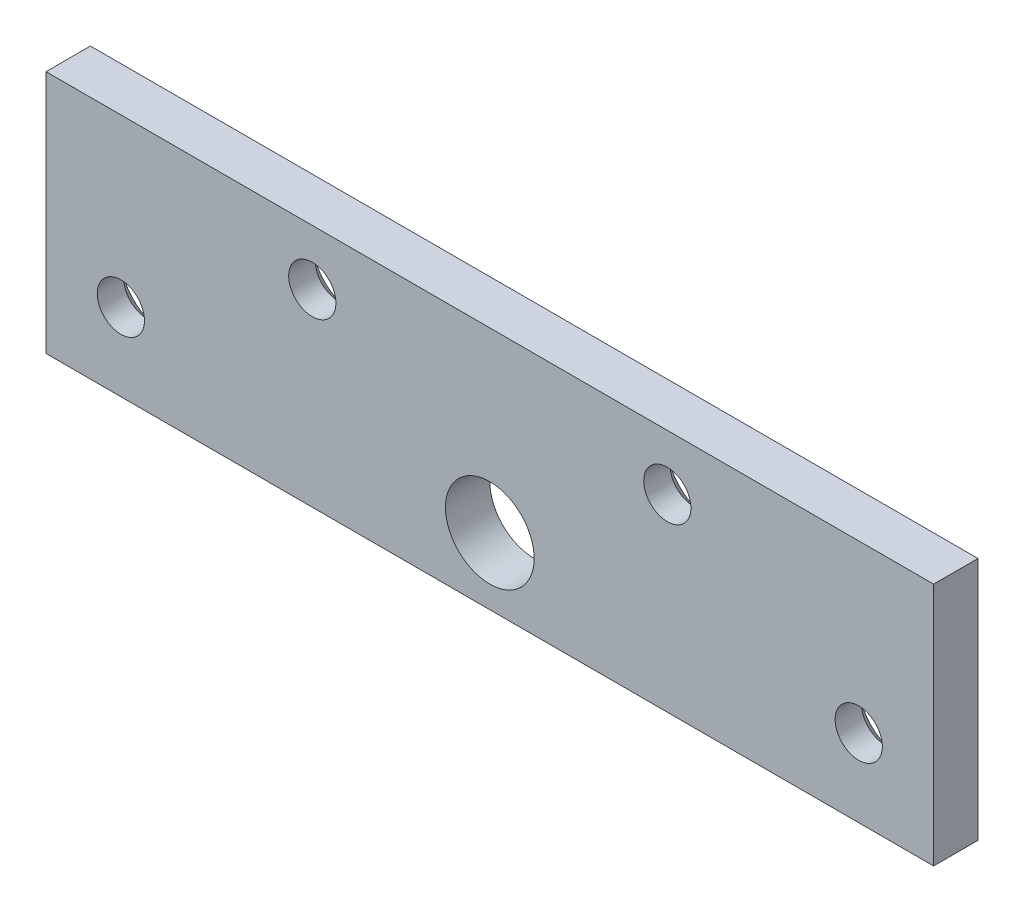
SolidWorks part; units mm, degrees
material "6061-T6 (SS)"
ref_plane "Front Plane" through (0, 0, 0) normal (0, 0, 1) x (1, 0, 0)
ref_plane "Top Plane" through (0, 0, 0) normal (0, 1, 0) x (1, 0, 0)
ref_plane "Right Plane" through (0, 0, 0) normal (1, 0, 0) x (0, 0, -1)
sketch "Sketch1" plane through (0, 0, 0) normal (0, 0, 1) x (1, 0, 0)
  line L0 (0, 15.875) -> (127, 15.875) construction
  line L1 (0, 0) -> (127, 0) construction
  line L2 (0, 0) -> (0, 31.75) construction
  line L3 (0, 31.75) -> (127, 31.75)
  line L4 (127, 0) -> (127, 31.75) construction
  line L5 (63.5, 0) -> (63.5, 31.75) construction
  line L6 (0, 31.75) -> (0, -3.175)
  line L7 (0, -3.175) -> (127, -3.175)
  line L8 (127, -3.175) -> (127, 31.75)
  circle A0 centre (63.5, 6.35) radius 6.35
  dimension "D3" = 12.7
  dimension "D1" = 31.75
  dimension "D2" = 127
  dimension "D4" = 9.525
  dimension "D5" = 19.05
extrude "Boss-Extrude1" add sketch "Sketch1" along normal blind 6.35
hole_wizard "CSK for 1/4 Flat Head Machine Screw (100)2" positions "Sketch6" profile "Sketch7" countersink size "1/4" standard "ANSI Inch" end condition through all
sketch "Sketch6" plane through (248.3324, -44.45, 0) normal (0, 0, -1) x (-1, 0, 0)
  line L0 (184.8324, 76.2) -> (184.8324, 60.325) construction
  line L3 (159.4324, 68.2625) -> (210.2324, 68.2625) construction
  line L4 (142.7653, 52.3875) -> (121.3324, 52.3875) construction
  line L7 (226.8995, 52.3875) -> (248.3324, 52.3875) construction
  point P0 (210.2324, 68.2625)
  point P22 (159.4324, 68.2625)
  point P23 (132.0489, 52.3875)
  point P24 (237.616, 52.3875)
sketch "Sketch7" plane through (38.1, 23.8125, 0) normal (1, 0, 0) x (0, 1, 0)
  line L0 (0, 0) -> (0, 6.35)
  line L1 (0, 6.35) -> (3.3782, 6.35)
  line L2 (3.3782, 6.35) -> (3.3782, 2.5682)
  line L3 (3.3782, 2.5682) -> (6.4389, 0)
  line L4 (6.4389, 0) -> (0, 0)
  line L5 (-3.3782, 2.5682) -> (-6.4389, 0) construction
  line L6 (0, -6.35) -> (0, 107.95) construction
  dimension "Thru Hole Dia." = 6.7564
  dimension "Thru Hole Depth" = 6.35
  dimension "Near C'Sink Dia." = 12.8778
  dimension "Near C'Sink Angle" = 100
equation "\"dovetail-angle\" = 55"
equation "\"dovetail-stock-width\" = 5"
equation "\"dovetail-stock-height\" = 1.25"
equation "\"dovetail-depth\" = 0.5 * \"dovetail-stock-height\""
equation "\"dovetail-throat-width\" = \"dovetail-stock-width\" - (2 * \"dovetail-depth\")"
equation "\"delta-x\" = 6"
equation "\"delta-y\" = 3"
equation "\"gib-thickness\" = 0.25"
equation "\"x-slide-length\" = \"dovetail-stock-width\" + \"delta-x\""
equation "\"y-slide-length\" = \"dovetail-stock-width\" + \"delta-y\""
equation "\"dog-point-diam\" = .149"
equation "\"dog-point-length\" = .067"
equation "\"dovetail-double-height\" = 2 * \"dovetail-depth\" + 0.5"
equation "\"acme-major-diam\" = .5"
equation "\"acme-pitch-diam\" = 0.45"
equation "\"acme-minor-diam\" = 0.4"
equation "\"x-screw-length\" = \"x-slide-length\" + \"screw-add-length\""
equation "\"y-screw-length\" = \"y-slide-length\" + \"screw-add-length\""
equation "\"acme-nut-od\" = 1.47"
equation "\"acme-nut-length\" = 1"
equation "\"acme-nut-trim-height\" = .75"
equation "\"D1@Sketch1\"=\"dovetail-stock-height\""
equation "\"D2@Sketch1\"=\"dovetail-stock-width\""
equation "\"screw-bearing-od\" = 0.5"
equation "\"screw-bearing-length\" = .25"
equation "\"D3@Sketch1\"=\"screw-bearing-od\""
equation "\"end-plate-thickness\" = \"screw-bearing-length\""
equation "\"D1@Boss-Extrude1\"=\"end-plate-thickness\""
equation "\"D4@Sketch1\"=\"acme-nut-trim-height\"/2"
equation "\"D5@Sketch1\"=\"acme-nut-trim-height\""
equation "\"screw-bearing-id\" = .375"
equation "\"screw-add-length\" = 2 * \"end-plate-thickness\" + 1 + 0.5"
equation "\"acme-nut-mount-hole-space-horz\" = 0.82"
equation "\"acme-nut-mount-hole-space-vert\" = 0.5 * \"acme-nut-length\""
